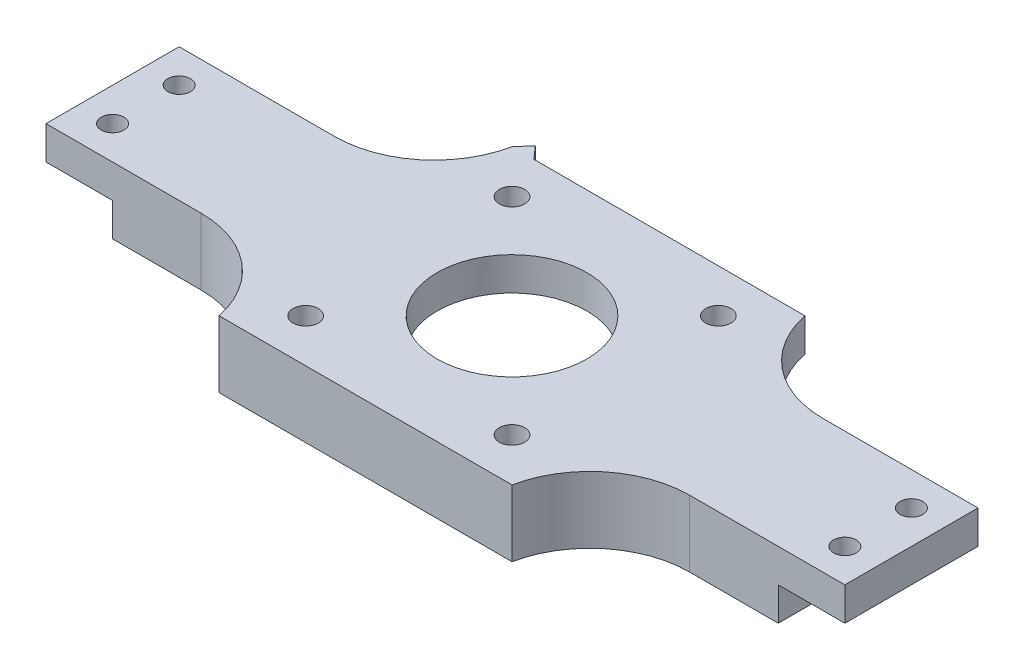
SolidWorks part; units mm, degrees
ref_plane "Ebene vorne" through (0, 0, 0) normal (0, 0, 1) x (1, 0, 0)
ref_plane "Ebene oben" through (0, 0, 0) normal (0, 1, 0) x (1, 0, 0)
ref_plane "Ebene rechts" through (0, 0, 0) normal (1, 0, 0) x (0, 0, -1)
sketch "Skizze1" plane through (0, 0, 0) normal (0, 1, 0) x (1, 0, 0)
  line L0 (-60, -4.8) -> (-22, -4.8)
  line L1 (60, -4.8) -> (60, 15.2)
  line L2 (60, 15.2) -> (22, 15.2)
  line L3 (0, 10.4) -> (0, 0) construction
  line L4 (-60, -4.8) -> (-60, 15.2)
  line L5 (22, -4.8) -> (60, -4.8)
  line L6 (-22, 15.2) -> (-22, 27.2)
  line L7 (-15.5, -10.3) -> (15.5, -10.3) construction
  line L8 (-15.5, -10.3) -> (-15.5, 20.7) construction
  line L9 (-15.5, 20.7) -> (15.5, 20.7) construction
  line L10 (15.5, -10.3) -> (15.5, 20.7) construction
  line L11 (-15.5, -10.3) -> (15.5, 20.7) construction
  line L12 (-15.5, 20.7) -> (15.5, -10.3) construction
  line L13 (-22, -16.8) -> (22, -16.8)
  line L14 (-22, -16.8) -> (-22, -4.8)
  line L15 (-22, 27.2) -> (0, 27.2)
  line L16 (22, -16.8) -> (22, -4.8)
  line L17 (-22, -16.8) -> (22, 27.2) construction
  line L18 (-22, 27.2) -> (22, -16.8) construction
  line L19 (22, 15.2) -> (22, 27.2)
  line L20 (-22, 15.2) -> (-60, 15.2)
  line L21 (0, 5.2) -> (-66.3854, 5.2) construction
  line L22 (0, 5.2) -> (0, 50.559) construction
  line L23 (0, 27.2) -> (22, 27.2)
  point P7 (0, 5.2)
  point P8 (0, 5.2)
  point P11 (-60, 5.2)
  dimension "D3" = 31
  dimension "D1" = 120
  dimension "D2" = 20
  dimension "D4" = 44
  dimension "D5" = 44
extrude "Aufsatz-Linear austragen1" add sketch "Skizze1" along normal blind 10
sketch "Skizze4" plane through (-60, 0, 0) normal (1, 0, 0) x (0, 0, -1)
  line L0 (-4.8, 10) -> (15.2, 10)
  line L1 (15.2, 10) -> (15.2, 9.0736)
  line L2 (15.2, 10) -> (15.2, 0) construction
  line L3 (-4.8, 10) -> (-4.8, 5.2708)
  line L4 (-4.8, 10) -> (-4.8, 0) construction
  arc A1 (-4.8, 5.2708) -> (15.2, 9.0736) centre (58.0172, -270.6068) cw
extrude "Schnitt-Linear austragen2" [suppressed] cut sketch "Skizze4" along normal blind 10
fillet "Verrundung1" [suppressed] radius 10
mirror "Spiegeln1" [suppressed] about plane through (0, 0, 0) normal (1, 0, 0)
sketch "Skizze6" plane through (0, 10, 0) normal (0, 1, 0) x (1, 0, 0)
  line L0 (0, 27.2) -> (0, -16.8) construction
  line L3 (22, 27.2) -> (-22, 27.2) construction
  line L4 (-15.5, -10.3) -> (15.5, -10.3) construction
  line L5 (-15.5, -10.3) -> (-15.5, 20.7) construction
  line L6 (-15.5, 20.7) -> (15.5, 20.7) construction
  line L7 (15.5, -10.3) -> (15.5, 20.7) construction
  line L8 (-15.5, -10.3) -> (15.5, 20.7) construction
  line L9 (-15.5, 20.7) -> (15.5, -10.3) construction
  line L10 (-22, -16.8) -> (22, -16.8) construction
  circle A0 centre (15.5, 20.7) radius 1.9
  circle A1 centre (15.5, -10.3) radius 1.9
  circle A2 centre (-15.5, -10.3) radius 1.9
  circle A3 centre (-15.5, 20.7) radius 1.9
  circle A4 centre (0, 5.2) radius 11.25
  point P6 (0, 5.2)
  dimension "D2" = 3.8
  dimension "D3" = 22.5
  dimension "D1" = 31
extrude "Schnitt-Linear austragen4" cut sketch "Skizze6" against normal through all
sketch "Skizze7" plane through (-22, 0, 0) normal (-1, 0, 0) x (0, 0, 1)
  line L0 (-36.0808, 5) -> (-15.2, 5)
  line L2 (-15.2, 10) -> (-15.2, 0) construction
  line L3 (-15.2, 5) -> (-15.2, 0)
  line L4 (-15.2, 0) -> (-36.0808, 0)
  line L6 (-36.0808, 5) -> (-36.0808, 0)
extrude "Schnitt-Linear austragen5" cut sketch "Skizze7" against normal through all
fillet "Verrundung2" [suppressed] radius 10
fillet "Verrundung3" radius 15 4 edges at (-22, 7.5, -15.2) (-22, 5, 4.8) (22, 5, 4.8) (22, 7.5, -15.2)
fillet "Verrundung4" [suppressed] radius 22
sketch "Skizze8" plane through (0, 0, -15.2) normal (0, 0, -1) x (-1, 0, 0)
  line L6 (-60, 5) -> (-50, 5)
  line L7 (-60, 10) -> (-60, 0) construction
  line L8 (-50, 5) -> (-50, 0)
  line L9 (-60, 0) -> (-5.1539, 0) construction
  line L10 (-50, 0) -> (-60, 0)
  line L11 (-60, 0) -> (-60, 5)
  line L12 (0, 0) -> (0, 15.1362) construction
  line L13 (-11.25, 0) -> (11.25, 0) construction
  line L14 (60, 0) -> (60, 5)
  line L15 (50, 0) -> (60, 0)
  line L16 (50, 5) -> (50, 0)
  line L17 (60, 5) -> (50, 5)
  dimension "D1" = 10
extrude "Schnitt-Linear austragen6" cut sketch "Skizze8" against normal through all and the other way through all
sketch "Skizze9" plane through (0, 5, 0) normal (0, -1, 0) x (1, 0, 0)
  line L0 (-60, -5.2) -> (-50, -5.2) construction
  line L1 (-60, 4.8) -> (-60, -15.2) construction
  line L2 (-50, 4.8) -> (-50, -15.2) construction
  line L3 (-55, -5.2) -> (-55, 4.8) construction
  line L4 (-60, 4.8) -> (-50, 4.8) construction
  line L5 (0, 0) -> (0, -8.3592) construction
  circle A0 centre (-55, -0.2) radius 1.7
  circle A1 centre (-55, -10.2) radius 1.7
  circle A2 centre (55, -10.2) radius 1.7
  circle A3 centre (55, -0.2) radius 1.7
  dimension "D1" = 3.4
extrude "Schnitt-Linear austragen7" cut sketch "Skizze9" against normal blind 10
sketch "Skizze10" plane through (0, 10, 0) normal (0, 1, 0) x (1, 0, 0)
  line L0 (-22, 27.2) -> (-20.3604, 29.0682)
  line L1 (-20.3604, 29.0682) -> (-20.3604, 27.2) construction
  line L2 (22, 27.2) -> (-22, 27.2) construction
  line L3 (-18.7207, 27.2) -> (-20.3604, 29.0682)
  line L4 (-18.7207, 27.2) -> (-22, 27.2)
extrude "Aufsatz-Linear austragen2" add sketch "Skizze10" against normal blind 5
sketch "Skizze11" plane through (0, 10, 0) normal (0, 1, 0) x (1, 0, 0)
  line L0 (23.7415, 47.7995) -> (24.8232, 40.4162) construction
  line L1 (24.8232, 40.4162) -> (25.9159, 32.9579) construction
  line L2 (25.9159, 32.9579) -> (25.9159, 14.8182) construction
  line L3 (25.9159, 29.3005) -> (27.5941, 27.3005)
  line L4 (25.9159, 29.3005) -> (24.2377, 27.3005)
  line L5 (24.2377, 27.3005) -> (22, 27.2)
  line L6 (27.5941, 27.3005) -> (28.9419, 17.3602)
  line L7 (28.9419, 17.3602) -> (24.0809, 17.5461)
  line L8 (24.0809, 17.5461) -> (21.4223, 25.8471)
  line L9 (21.4223, 25.8471) -> (22, 27.2)
  arc A0 (-127.1113, 338.6796) -> (126.7578, 338.6796) centre (-0.1768, 211.0567) ccw construction
  arc A1 (22, 27.2) -> (36.6969, 15.2) centre (36.6969, 30.2) ccw construction
  dimension "D1" = 2
  dimension "D2" = 40
extrude "Aufsatz-Linear austragen3" [suppressed] add sketch "Skizze11" against normal up to vertex up to point (22, 5, -27.2)
fillet "Verrundung5" [suppressed] radius 3
chamfer "Fase1" distance 28 angle 35 2 edges at (-5.1539, 2.5, -15.2) (5.1539, 2.5, -15.2) first distance on face at (-37.9627, 5, -15.2) first distance on face at (37.9627, 5, -15.2)
fillet "Verrundung6" radius 10 4 edges at (-33.1539, 2.5, -15.2) (33.1539, 2.5, -15.2) (-8.7186, 2.5, 1.9098) (8.7186, 2.5, 1.9098)
